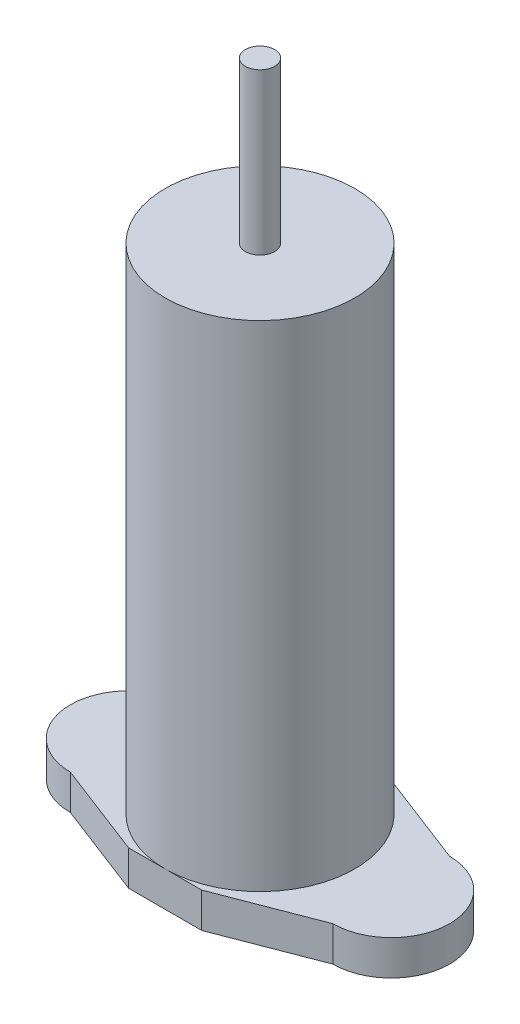
SolidWorks part; units mm, degrees
ref_plane "Спереди" through (0, 0, 0) normal (0, 0, 1) x (1, 0, 0)
ref_plane "Сверху" through (0, 0, 0) normal (0, 1, 0) x (1, 0, 0)
ref_plane "Справа" through (0, 0, 0) normal (1, 0, 0) x (0, 0, -1)
sketch "Эскиз1" plane through (0, 0, 0) normal (0, 1, 0) x (1, 0, 0)
  line L0 (-2.5056, 6.5) -> (2.5056, 6.5)
  line L1 (-9, 4) -> (-2.5056, 6.5)
  line L2 (-9, 0) -> (9, 0) construction
  line L3 (2.5056, 6.5) -> (9, 4)
  line L4 (2.5056, -6.5) -> (9, -4)
  line L5 (-2.5056, -6.5) -> (2.5056, -6.5)
  line L6 (-9, -4) -> (-2.5056, -6.5)
  circle A0 centre (0, 0) radius 9 construction
  circle A1 centre (0, 0) radius 6.5
  circle A2 centre (9, 0) radius 4
  circle A3 centre (-9, 0) radius 4
  point P10 (0, 6.5)
  dimension "D1" = 13
  dimension "D2" = 18
  dimension "D3" = 8
  dimension "D4" = 8
extrude "Бобышка-Вытянуть1" add sketch "Эскиз1" along normal blind 2.4 contours A3 A1 | A3 A1 L0 L1 | A3 A1 A2 | A1 A3 | A3 L6 L5 A1 | A1 A2 | A2 L3 L0 A1 | A2 A1 | A2 A1 L5 L4 region at (-5.4639, 0, -4.6501) region at (5.4639, 0, -4.6501) region at (0, 0, 0) region at (-9.3788, 0, 0) region at (9.3788, 0, 0) region at (5.7868, 0, 0) region at (-5.7868, 0, 0) region at (-5.4639, 0, 4.6501) region at (5.4639, 0, 4.6501)
extrude "Бобышка-Вытянуть2" add sketch "Эскиз1<3>" along normal blind 36.3 contours A3 A1 A2 | A1 A3 | A1 A2 region at (0, 0, 0) region at (5.7868, 0, 0) region at (-5.7868, 0, 0)
sketch "Эскиз1<3>" plane through (0, 0, 0) normal (0, 1, 0) x (1, 0, 0) same geometry as "Эскиз1"
sketch "Эскиз2" plane through (0, 36.3, 0) normal (0, 1, 0) x (1, 0, 0)
  circle A0 centre (0, 0) radius 1
  dimension "D1" = 2
extrude "Бобышка-Вытянуть3" add sketch "Эскиз2" along normal blind 11
